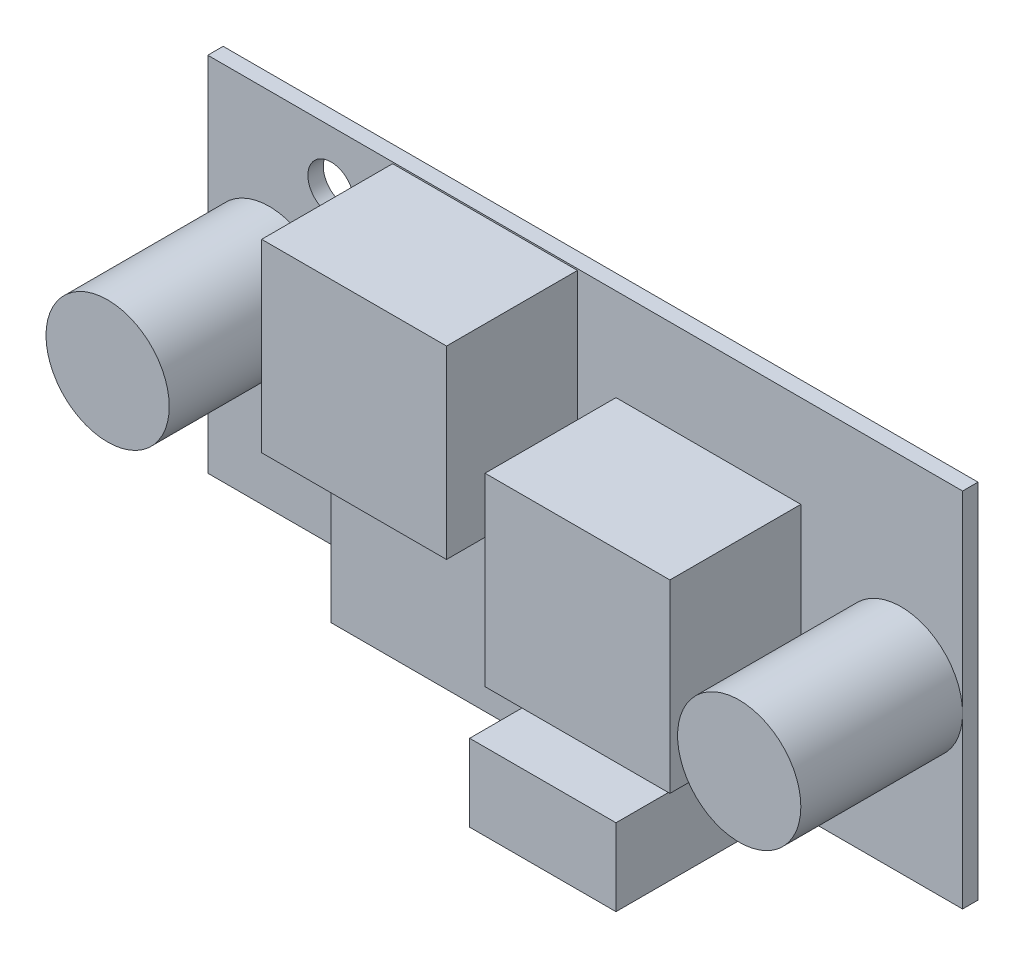
SolidWorks part; units mm, degrees
ref_plane "Спереди" through (0, 0, 0) normal (0, 0, 1) x (1, 0, 0)
ref_plane "Сверху" through (0, 0, 0) normal (0, 1, 0) x (1, 0, 0)
ref_plane "Справа" through (0, 0, 0) normal (1, 0, 0) x (0, 0, -1)
sketch "Эскиз1" plane through (0, 0, 0) normal (0, 0, 1) x (1, 0, 0)
  line L0 (0, 0) -> (-16.5, 8.25) construction
  line L1 (-24.5, 11.75) -> (24.5, 11.75)
  line L2 (-24.5, 11.75) -> (-24.5, -11.75)
  line L3 (-24.5, -11.75) -> (24.5, -11.75)
  line L4 (24.5, 11.75) -> (24.5, -11.75)
  line L5 (-24.5, 11.75) -> (24.5, -11.75) construction
  line L6 (-24.5, -11.75) -> (24.5, 11.75) construction
  circle A1 centre (-16.5, 8.25) radius 1.5
  circle A2 centre (16.5, -8.25) radius 1.5
  point P0 (0, 0)
  dimension "D1" = 49
  dimension "D3" = 3
  dimension "D2" = 23.5
  dimension "D4" = 8
  dimension "D5" = 3.5
extrude "Плата-основа" add sketch "Эскиз1" along normal blind 1
sketch "Эскиз2" plane through (0, 0, 1) normal (0, 0, 1) x (1, 0, 0)
  line L0 (-24.5, 11.75) -> (-24.5, -11.75) construction
  line L1 (-12.5, 11.65) -> (-0.5, 11.65)
  line L2 (-12.5, 11.65) -> (-12.5, -0.35)
  line L3 (-12.5, -0.35) -> (-0.5, -0.35)
  line L4 (-0.5, 11.65) -> (-0.5, -0.35)
  line L5 (-12.5, 11.65) -> (-0.5, -0.35) construction
  line L6 (-12.5, -0.35) -> (-0.5, 11.65) construction
  line L7 (4, -6.65) -> (13.5, -6.65)
  line L8 (4, -6.65) -> (4, -11.65)
  line L9 (4, -11.65) -> (13.5, -11.65)
  line L10 (13.5, -6.65) -> (13.5, -11.65)
  line L11 (4, -6.65) -> (13.5, -11.65) construction
  line L12 (4, -11.65) -> (13.5, -6.65) construction
  line L13 (2, 5.75) -> (14, 5.75)
  line L14 (2, 5.75) -> (2, -6.25)
  line L15 (2, -6.25) -> (14, -6.25)
  line L16 (14, 5.75) -> (14, -6.25)
  line L17 (2, 5.75) -> (14, -6.25) construction
  line L18 (2, -6.25) -> (14, 5.75) construction
  line L19 (24.5, 11.75) -> (-24.5, 11.75) construction
  line L20 (-24.5, -11.75) -> (24.5, -11.75) construction
  line L21 (24.5, -11.75) -> (24.5, 11.75) construction
  line L23 (-12, -1.65) -> (1, -1.65)
  line L24 (-12, -1.65) -> (-12, -11.65)
  line L25 (-12, -11.65) -> (1, -11.65)
  line L26 (1, -1.65) -> (1, -11.65)
  line L27 (-12, -1.65) -> (1, -11.65) construction
  line L28 (-12, -11.65) -> (1, -1.65) construction
  circle A0 centre (-20.5, 1.25) radius 4
  circle A1 centre (20.5, -0.75) radius 4
  point P2 (-6.5, 5.65)
  point P7 (8.75, -9.15)
  point P12 (8, -0.25)
  point P21 (-5.5, -6.65)
  line M8 (24.5, 11.75) -> (-24.5, 11.75)
  line M10 (-24.5, -11.75) -> (24.5, -11.75)
  dimension "D1" = 8
  dimension "D2" = 10.5
  dimension "D3" = 12
  dimension "D4" = 9.5
  dimension "D5" = 5
  dimension "D6" = 11
  dimension "D7" = 11
  dimension "D8" = 12
  dimension "D9" = 10.5
  dimension "D10" = 6
  dimension "D11" = 10
  dimension "D12" = 13
  dimension "D13" = 12.5
  dimension "D14" = 0.1
  dimension "D15" = 0.1
extrude "Конденсаторы" add sketch "Эскиз2" along normal blind 10.5 contours A0 | A1 | A0 | A1 region at (-20.5, 1.25, 1) region at (20.5, -0.75, 1)
extrude "Регулятор" add sketch "Эскиз2<3>" along normal blind 11.5 contours L10 L7 L8 M10 region at (8.75, -9.15, 1)
sketch "Эскиз2<3>" plane through (0, 0, 1) normal (0, 0, 1) x (1, 0, 0) same geometry as "Эскиз2"
extrude "Какая то штука" add sketch "Эскиз2<5>" along normal blind 8.5 contours L4 L2 L3 M8 | L16 L13 L14 L15 region at (-6.5, 5.65, 1) region at (8, -0.25, 1)
sketch "Эскиз2<5>" plane through (0, 0, 1) normal (0, 0, 1) x (1, 0, 0) same geometry as "Эскиз2"
extrude "Микросхема" add sketch "Эскиз2<6>" along normal blind 4.5 contours L26 L23 L24 M10 region at (-5.5, -6.65, 1)
sketch "Эскиз2<6>" plane through (0, 0, 1) normal (0, 0, 1) x (1, 0, 0) same geometry as "Эскиз2"
